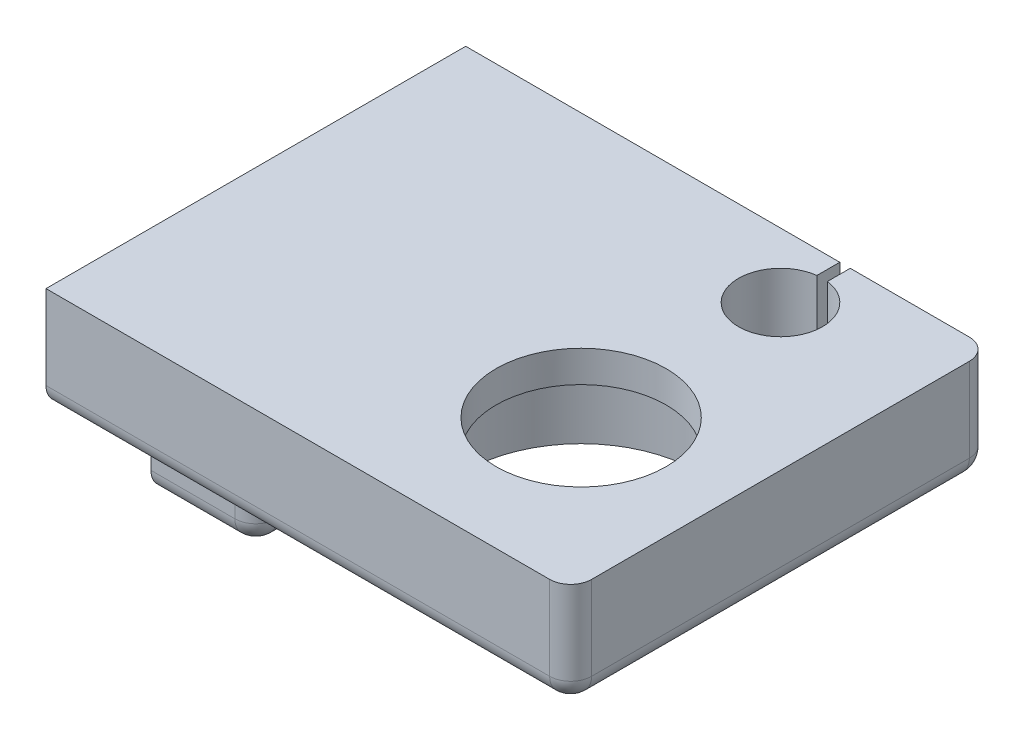
SolidWorks part; units mm, degrees
ref_plane "Front Plane" through (0, 0, 0) normal (0, 0, 1) x (1, 0, 0)
ref_plane "Top Plane" through (0, 0, 0) normal (0, 1, 0) x (1, 0, 0)
ref_plane "Right Plane" through (0, 0, 0) normal (1, 0, 0) x (0, 0, -1)
sketch "Sketch2" plane through (0, 0, 0) normal (0, 1, 0) x (1, 0, 0)
  line L0 (36.15, -6.15) -> (36.15, -25.15) construction
  line L1 (0, 0) -> (50, 0)
  line L2 (0, 0) -> (0, -40)
  line L3 (0, -40) -> (50, -40)
  line L4 (50, 0) -> (50, -40)
  line L5 (36.15, -2.1814) -> (36.15, -6.15) construction
  line L6 (35.65, 0) -> (36.65, 0)
  line L7 (35.65, 0) -> (35.65, -2.1814)
  line L8 (35.65, -2.1814) -> (36.65, -2.1814)
  line L9 (36.65, 0) -> (36.65, -2.1814)
  line L10 (36.15, -25.15) -> (36.15, -33.2346) construction
  line L12 (35.65, -40) -> (36.65, -40)
  line L13 (35.65, -40) -> (35.65, -33.2346) construction
  line L14 (35.65, -33.2346) -> (36.65, -33.2346)
  line L15 (36.65, -40) -> (36.65, -33.2346) construction
  circle A2 centre (36.15, -6.15) radius 4
  circle A3 centre (36.15, -25.15) radius 11.1 construction
  circle A4 centre (36.15, -25.15) radius 8.1
  dimension "D3" = 13.85
  dimension "D4" = 6.15
  dimension "D5" = 19
  dimension "D6" = 50
  dimension "D7" = 40
  dimension "D8" = 1
  dimension "D1" = 22.2
  dimension "D2" = 8
  dimension "D9" = 3
  dimension "D10" = 1
extrude "Boss-Extrude1" add sketch "Sketch2" along normal blind 10 contours L4 L1 L2 L3 A2 region at (23.3446, 0, 19.8137)
sketch "Sketch3" plane through (0, 0, 0) normal (0, -1, 0) x (1, 0, 0)
  circle A0 centre (36.15, 25.15) radius 11.1 construction
  circle A1 centre (36.15, 25.15) radius 11.1
  circle A2 centre (36.15, 25.15) radius 8.1
  circle A3 centre (36.15, 25.15) radius 8.1 construction
extrude "Cut-Extrude1" cut sketch "Sketch3" against normal blind 7
sketch "Sketch6" plane through (0, 0, 0) normal (0, 0, -1) x (-1, 0, 0)
  line L1 (0, 0) -> (-10, 0)
  line L2 (0, 0) -> (0, -12)
  line L3 (0, -12) -> (-10, -12)
  line L4 (-10, 0) -> (-10, -12)
  dimension "D1" = 12
  dimension "D2" = 10
extrude "Boss-Extrude4" add sketch "Sketch6" against normal blind 30
sketch "Sketch7" plane through (10, 0, 0) normal (1, 0, 0) x (0, 0, -1)
  line L0 (-9, -5) -> (0, -5) construction
  line L2 (-9, -5) -> (-21, -5) construction
  line L3 (-21, -5) -> (-30, -5) construction
  line L5 (0, 0) -> (0, -12) construction
  line L6 (-30, 0) -> (-30, -12) construction
  line L8 (0, 0) -> (-40, 0) construction
  circle A0 centre (-9, -5) radius 2.8
  circle A2 centre (-21, -5) radius 2.8
  point P3 (0, 0)
  point P6 (0, -4.7279)
  point P7 (0, -4.7279)
  point P10 (-30, -4.7279)
  dimension "D1" = 5.6
  dimension "D2" = 12
  dimension "D3" = 5
extrude "Cut-Extrude2" cut sketch "Sketch7" against normal through all
sketch "Sketch8" plane through (10, 0, 0) normal (1, 0, 0) x (0, 0, -1)
  circle A0 centre (-21, -5) radius 4.3
  circle A2 centre (-9, -5) radius 4.3
  dimension "D1" = 8.6
extrude "Cut-Extrude3" cut sketch "Sketch8" against normal blind 6
fillet "Fillet1" radius 2 11 edges at (10, -6, 30) (25, 0, 40) (50, 5, 40) (50, 0, 20) (43.325, 0, 0) (10, -6, 0) (22.825, 0, 0) (50, 5, 0) (5, -12, 30) (5, -12, 0) (10, -12, 15)
